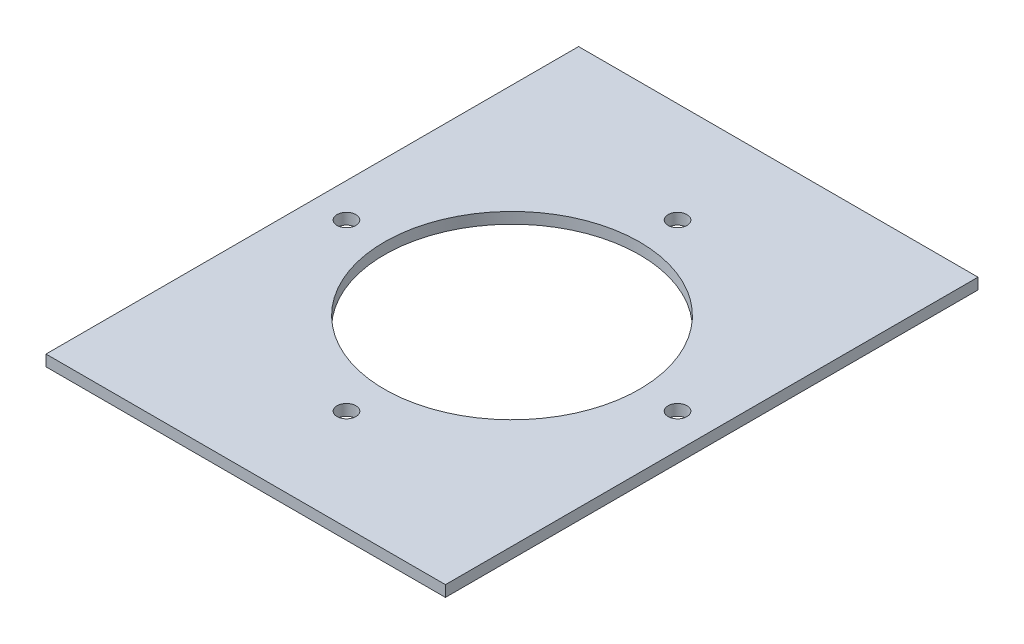
SolidWorks part; units mm, degrees
material "1.0553 (S355J0)"
ref_plane "Płaszczyzna przednia" through (0, 0, 0) normal (0, 0, 1) x (1, 0, 0)
ref_plane "Płaszczyzna górna" through (0, 0, 0) normal (0, 1, 0) x (1, 0, 0)
ref_plane "Płaszczyzna prawa" through (0, 0, 0) normal (1, 0, 0) x (0, 0, -1)
sketch "Szkic1" plane through (0, 0, 0) normal (0, 1, 0) x (1, 0, 0)
  line L1 (-90, -120) -> (90, -120)
  line L2 (-90, -120) -> (-90, 120)
  line L3 (-90, 120) -> (90, 120)
  line L4 (90, -120) -> (90, 120)
  point P4 (0, 120)
  point P6 (90, 0)
  dimension "D4" = 180
  dimension "D5" = 240
extrude "Dodanie-wyciągnięcie1" add sketch "Szkic1" along normal blind 5
sketch "Szkic2" plane through (0, 0, 0) normal (0, 1, 0) x (1, 0, 0)
  circle A0 centre (0, 0) radius 57.5
  circle A1 centre (0, 74.6) radius 4.25
  dimension "D1" = 115
  dimension "D3" = 8.5
  dimension "D2" = 74.6
extrude "Wytnij-wyciągnięcie1" cut sketch "Szkic2" along normal blind 43
pattern_circular "Szyk kołowy1" count 4 every 90 about axis through (0, 5, 0) along (0, 1, 0) of "Wytnij-wyciągnięcie1"
sketch "Szkic3" [suppressed] plane through (0, 5, 0) normal (0, 1, 0) x (1, 0, 0)
  circle A0 centre (0, -53) radius 5.25
  circle A1 centre (0, 0) radius 37.5
  dimension "D1" = 10.5
  dimension "D3" = 75
  dimension "D2" = 53
extrude "Wytnij-wyciągnięcie2" [suppressed] cut sketch "Szkic3" against normal blind 10
pattern_circular "Szyk kołowy2" [suppressed] count 4 every 90 of bodies 105
